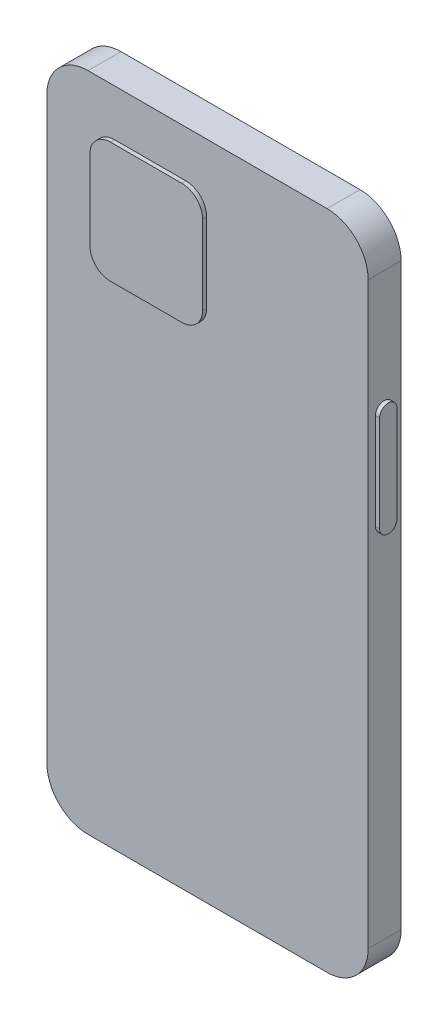
SolidWorks part; units mm, degrees
ref_plane "前视基准面" through (0, 0, 0) normal (0, 0, 1) x (1, 0, 0)
ref_plane "上视基准面" through (0, 0, 0) normal (0, 1, 0) x (1, 0, 0)
ref_plane "右视基准面" through (0, 0, 0) normal (1, 0, 0) x (0, 0, -1)
other "Configuration Table"
sketch "草图1" plane through (0, 0, 0) normal (0, 0, 1) x (1, 0, 0)
  line L1 (-29.05, 80.4) -> (29.05, 80.4)
  line L2 (-39.05, 70.4) -> (-39.05, -70.4)
  line L3 (-29.05, -80.4) -> (29.05, -80.4)
  line L4 (39.05, 70.4) -> (39.05, -70.4)
  line L5 (-39.05, 80.4) -> (39.05, -80.4) construction
  line L6 (-39.05, -80.4) -> (39.05, 80.4) construction
  arc A0 (-39.05, -70.4) -> (-29.05, -80.4) centre (-29.05, -70.4) ccw
  arc A1 (29.05, -80.4) -> (39.05, -70.4) centre (29.05, -70.4) ccw
  arc A2 (29.05, 80.4) -> (39.05, 70.4) centre (29.05, 70.4) cw
  arc A3 (-29.05, 80.4) -> (-39.05, 70.4) centre (-29.05, 70.4) ccw
  point P0 (0, 0)
  point P18 (0, 0)
  dimension "D3" = 10
  dimension "D1" = 160.8
  dimension "D2" = 78.1
extrude "凸台-拉伸1" add sketch "草图1" along normal blind 8
sketch "草图2" plane through (0, 0, 8) normal (0, 0, 1) x (1, 0, 0)
  line L1 (27.608, 79.0748) -> (-27.608, 79.0748)
  line L2 (37.608, 69.0748) -> (37.608, -69.0748)
  line L3 (27.608, -79.0748) -> (-27.608, -79.0748)
  line L4 (-37.608, 69.0748) -> (-37.608, -69.0748)
  line L5 (37.608, 79.0748) -> (-37.608, -79.0748) construction
  line L6 (37.608, -79.0748) -> (-37.608, 79.0748) construction
  arc A0 (37.608, -69.0748) -> (27.608, -79.0748) centre (27.608, -69.0748) cw
  arc A1 (-27.608, -79.0748) -> (-37.608, -69.0748) centre (-27.608, -69.0748) cw
  arc A2 (-27.608, 79.0748) -> (-37.608, 69.0748) centre (-27.608, 69.0748) ccw
  arc A3 (27.608, 79.0748) -> (37.608, 69.0748) centre (27.608, 69.0748) cw
  point P0 (0, 0)
  dimension "D1" = 10
sketch "草图3" plane through (39.05, 0, 0) normal (1, 0, 0) x (0, 0, -1)
  line L0 (-4.1157, 40.9381) -> (-4.1157, 17.5678) construction
  line L13 (-2.0103, 40.9381) -> (-2.0103, 17.5678)
  line L14 (-6.2212, 40.9381) -> (-6.2212, 17.5678)
  arc A12 (-2.0103, 40.9381) -> (-6.2212, 40.9381) centre (-4.1157, 40.9381) ccw
  arc A13 (-6.2212, 17.5678) -> (-2.0103, 17.5678) centre (-4.1157, 17.5678) ccw
  point P2 (-4.1157, 29.2529)
  point P7 (0, 0)
extrude "凸台-拉伸2" add sketch "草图3" along normal blind 1
sketch "草图4" plane through (-39.05, 0, 0) normal (-1, 0, 0) x (0, 0, 1)
  line L0 (3.4955, 59.2884) -> (3.4955, 51.3094) construction
  line L1 (4.9478, 59.2884) -> (4.9478, 51.3094)
  line L2 (2.0432, 59.2884) -> (2.0432, 51.3094)
  line L3 (3.4955, 40.4491) -> (3.4955, 25.3777) construction
  line L6 (4.9478, 40.4491) -> (4.9478, 25.3777)
  line L7 (2.0432, 40.4491) -> (2.0432, 25.3777)
  line L8 (3.4955, 21.1665) -> (3.4955, 4.322) construction
  line L13 (5.1694, 21.1665) -> (5.1694, 4.322)
  line L14 (1.8215, 21.1665) -> (1.8215, 4.322)
  arc A0 (4.9478, 59.2884) -> (2.0432, 59.2884) centre (3.4955, 59.2884) ccw
  arc A1 (2.0432, 51.3094) -> (4.9478, 51.3094) centre (3.4955, 51.3094) ccw
  arc A4 (4.9478, 40.4491) -> (2.0432, 40.4491) centre (3.4955, 40.4491) ccw
  arc A5 (2.0432, 25.3777) -> (4.9478, 25.3777) centre (3.4955, 25.3777) ccw
  arc A10 (5.1694, 21.1665) -> (1.8215, 21.1665) centre (3.4955, 21.1665) ccw
  arc A11 (1.8215, 4.322) -> (5.1694, 4.322) centre (3.4955, 4.322) ccw
  point P2 (3.4955, 55.2989)
  point P9 (3.4955, 32.9134)
  point P16 (3.4955, 12.7442)
  point P21 (3.4955, 51.5311)
  point P22 (3.4955, 59.2884)
  point P23 (0, 0)
  point P24 (3.4955, 32.9134)
  point P25 (3.4955, 12.7442)
  point P26 (0, 0)
sketch "草图5" plane through (-39.05, 0, 0) normal (-1, 0, 0) x (0, 0, 1)
  line L0 (3.4955, 60.1691) -> (3.4955, 50.6116) construction
  line L9 (4.0954, 60.1691) -> (4.0954, 50.6116)
  line L10 (2.8956, 60.1691) -> (2.8956, 50.6116)
  arc A10 (4.0954, 60.1691) -> (2.8956, 60.1691) centre (3.4955, 60.1691) ccw
  arc A11 (2.8956, 50.6116) -> (4.0954, 50.6116) centre (3.4955, 50.6116) ccw
  point P2 (3.4955, 55.3903)
  point P7 (0, 0)
  point P8 (0, 0)
  point P9 (0, 0)
  point P10 (0, 0)
  point P11 (0, 0)
extrude "凸台-拉伸4" add sketch "草图4" along normal blind 1
sketch "草图8" plane through (0, 0, 8) normal (0, 0, 1) x (1, 0, 0)
  line L5 (-22.608, 69.0748) -> (-5.2216, 69.0748)
  line L6 (-27.608, 64.0748) -> (-27.608, 44.7842)
  line L7 (-22.608, 39.7842) -> (-5.2216, 39.7842)
  line L8 (-0.2216, 64.0748) -> (-0.2216, 44.7842)
  arc A0 (-27.608, 44.7842) -> (-22.608, 39.7842) centre (-22.608, 44.7842) ccw
  arc A1 (-5.2216, 39.7842) -> (-0.2216, 44.7842) centre (-5.2216, 44.7842) ccw
  arc A2 (-5.2216, 69.0748) -> (-0.2216, 64.0748) centre (-5.2216, 64.0748) cw
  arc A3 (-22.608, 69.0748) -> (-27.608, 64.0748) centre (-22.608, 64.0748) ccw
  circle A6 centre (-6.8416, 61.4917) radius 5.0604
  circle A7 centre (-7.1996, 48.0673) radius 5.1508
  circle A8 centre (-19.8483, 54.9287) radius 5.5487
  circle A11 centre (-19.8483, 64.5942) radius 1.7303
  circle A12 centre (-19.8483, 44.7842) radius 1.6722
  circle A13 centre (-24.1441, 48.0673) radius 1.1588
  circle A14 centre (-6.8416, 61.4917) radius 2.7263
  circle A15 centre (-7.1996, 48.0673) radius 2.1996
  circle A16 centre (-19.8483, 54.9287) radius 3.0638
  circle A17 centre (-6.8416, 61.4917) radius 0.895
  circle A19 centre (-6.8416, 48.0673) radius 0.8005
  circle A20 centre (-19.8483, 54.9287) radius 1.0739
  point P14 (-27.608, 69.0748)
  point P33 (0, 0)
  point P34 (0, 0)
  dimension "D1" = 5
sketch "草图11" plane through (0, 0, 0) normal (0, 0, -1) x (-1, 0, 0)
extrude "凸台-拉伸13" add sketch "草图8" along normal blind 1 contours L8 A1 L7 A0 L6 A3 L5 A2
sketch "草图12" plane through (0, -80.4, 0) normal (0, -1, 0) x (1, 0, 0)
  line L0 (-4.6923, 4.0032) -> (4.0097, 4.0032) construction
  line L3 (-4.6923, 5.027) -> (4.0097, 5.027)
  line L4 (-4.6923, 2.9794) -> (4.0097, 2.9794)
  circle A1 centre (-19.7075, 4.0032) radius 0.8
  circle A2 centre (-17.0627, 4.0032) radius 0.8
  circle A4 centre (-14.1621, 4.0032) radius 0.8
  circle A5 centre (-11.5174, 4.0032) radius 0.8
  arc A8 (-4.6923, 5.027) -> (-4.6923, 2.9794) centre (-4.6923, 4.0032) ccw
  arc A9 (4.0097, 2.9794) -> (4.0097, 5.027) centre (4.0097, 4.0032) ccw
  circle A10 centre (9.7258, 4.0032) radius 0.8
  circle A12 centre (16.4655, 4.0032) radius 0.8
  circle A13 centre (20.134, 4.0032) radius 0.8
  circle A15 centre (13.1383, 4.0032) radius 0.8
  point P10 (-0.3413, 4.0032)
sketch "草图13" plane through (0, 0, 9) normal (0, 0, 1) x (1, 0, 0)
  circle A1 centre (-19.7482, 61.6503) radius 5.9919
  circle A2 centre (-19.7482, 48.6393) radius 5.99
  circle A3 centre (-7.6716, 55.1089) radius 5.99
  circle A5 centre (-7.6716, 65.604) radius 1.5815
  circle A6 centre (-7.6716, 43.248) radius 1.7971
  circle A7 centre (-2.3522, 48.6393) radius 1.0783
  circle A8 centre (-19.7482, 61.6503) radius 4.0049
  circle A9 centre (-19.7482, 48.6393) radius 4
  circle A10 centre (-7.6716, 55.1089) radius 4
sketch "草图14" plane through (0, 0, 0) normal (0, 0, -1) x (-1, 0, 0)
  line L0 (-10.6387, 72.3651) -> (12.4118, 72.3651) construction
  line L1 (-10.6387, 76.3546) -> (12.4118, 76.3546)
  line L2 (-10.6387, 68.3756) -> (12.4118, 68.3756)
  line L3 (-7.7574, 72.3651) -> (3.3246, 72.3651) construction
  line L6 (-7.7574, 75.2464) -> (3.3246, 75.2464)
  line L7 (-7.7574, 69.4838) -> (3.3246, 69.4838)
  arc A0 (-10.6387, 76.3546) -> (-10.6387, 68.3756) centre (-10.6387, 72.3651) ccw
  arc A1 (12.4118, 68.3756) -> (12.4118, 76.3546) centre (12.4118, 72.3651) ccw
  circle A4 centre (9.7521, 72.3651) radius 3.1029
  arc A5 (-7.7574, 75.2464) -> (-7.7574, 69.4838) centre (-7.7574, 72.3651) ccw
  arc A6 (3.3246, 69.4838) -> (3.3246, 75.2464) centre (3.3246, 72.3651) ccw
  point P2 (0.8866, 72.3651)
  point P11 (-2.2164, 72.3651)
